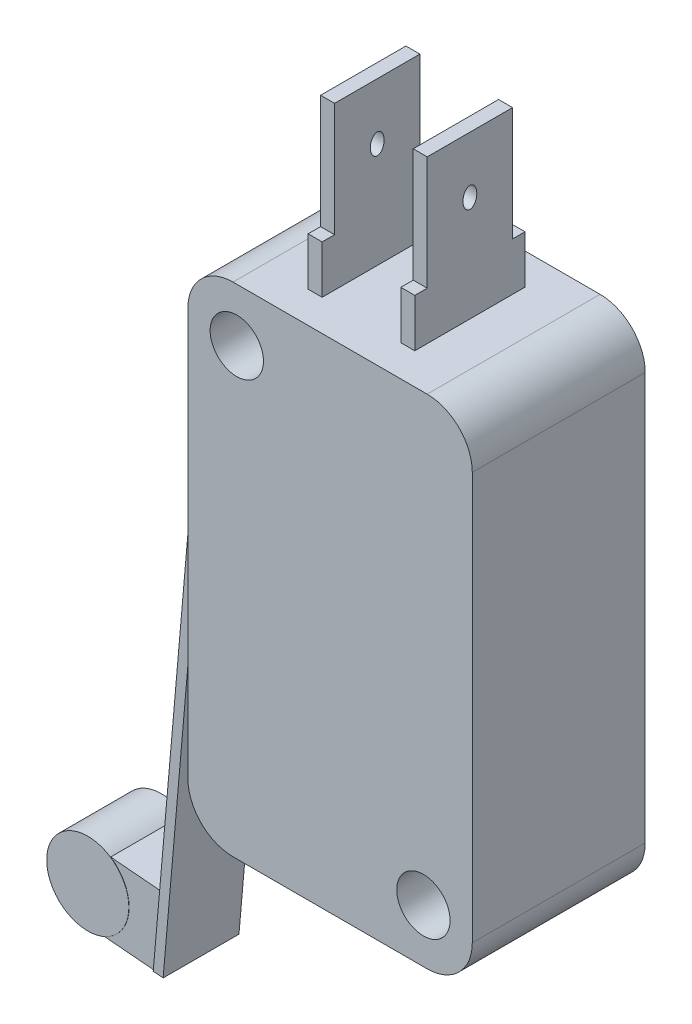
SolidWorks part; units mm, degrees
ref_plane "Front Plane" through (0, 0, 0) normal (0, 0, 1) x (1, 0, 0)
ref_plane "Top Plane" through (0, 0, 0) normal (0, 1, 0) x (1, 0, 0)
ref_plane "Right Plane" through (0, 0, 0) normal (1, 0, 0) x (0, 0, -1)
sketch "Sketch1" plane through (0, 0, 0) normal (0, 0, 1) x (1, 0, 0)
  line L1 (5.46, -14) -> (-5.46, -14)
  line L2 (8, -11.46) -> (8, 11.46)
  line L3 (5.46, 14) -> (-5.46, 14)
  line L4 (-8, -11.46) -> (-8, 11.46)
  line L5 (8, -14) -> (-8, 14) construction
  line L6 (8, 14) -> (-8, -14) construction
  arc A0 (5.46, -14) -> (8, -11.46) centre (5.46, -11.46) ccw
  arc A1 (-5.46, -14) -> (-8, -11.46) centre (-5.46, -11.46) cw
  arc A2 (8, 11.46) -> (5.46, 14) centre (5.46, 11.46) ccw
  arc A3 (-5.46, 14) -> (-8, 11.46) centre (-5.46, 11.46) ccw
  point P1 (0, 0)
  dimension "D3" = 2.54
  dimension "D1" = 28
  dimension "D2" = 16
extrude "Boss-Extrude1" add sketch "Sketch1" along normal mid plane 9.7282
ref_plane "Plane1" through (3, 0, 0) normal (1, 0, 0) x (0, 0, -1)
ref_plane "Plane2" through (-3, 0, 0) normal (1, 0, 0) x (0, 0, -1)
sketch "Sketch2" plane through (3, 0, 0) normal (1, 0, 0) x (0, 0, -1)
  line L0 (0, -3.2714) -> (0, 26.117) construction
  line L1 (-3.1, 14) -> (-3.1, 16.7)
  line L2 (-4.8641, 14) -> (4.8641, 14) construction
  line L3 (-3.1, 16.7) -> (-2.4, 16.7)
  line L4 (-2.4, 16.7) -> (-2.4, 23.1)
  line L5 (-2.4, 23.1) -> (2.4, 23.1)
  line L6 (2.4, 16.7) -> (2.4, 23.1)
  line L7 (3.1, 16.7) -> (2.4, 16.7)
  line L8 (3.1, 14) -> (3.1, 16.7)
  line L9 (3.1, 14) -> (-3.1, 14)
  ellipse E0 centre (0, 19.925) end of major axis (0, 19.3408) minor radius 0.388
  point P18 (0, 23.1)
  dimension "D1" = 6.2
  dimension "D2" = 0.5842
  dimension "D3" = 0.388
  dimension "D4" = 4.8
  dimension "D5" = 9.1
  dimension "D6" = 3.175
  dimension "D7" = 6.4
sketch "Sketch4" plane through (-3, 0, 0) normal (1, 0, 0) x (0, 0, -1)
  line L8 (2.4, 16.7) -> (2.4, 23.1)
  line L9 (3.1, 16.7) -> (2.4, 16.7)
  line L10 (3.1, 14) -> (3.1, 16.7)
  line L11 (-3.1, 14) -> (3.1, 14)
  line L12 (-3.1, 16.7) -> (-3.1, 14)
  line L13 (-2.4, 16.7) -> (-3.1, 16.7)
  line L14 (-2.4, 23.1) -> (-2.4, 16.7)
  line L15 (2.4, 23.1) -> (-2.4, 23.1)
  line L16 (2.4, 16.7) -> (2.4, 23.1)
  line L17 (3.1, 16.7) -> (2.4, 16.7)
  line L18 (3.1, 14) -> (3.1, 16.7)
  line L19 (-3.1, 14) -> (3.1, 14)
  line L20 (-3.1, 16.7) -> (-3.1, 14)
  line L21 (-2.4, 16.7) -> (-3.1, 16.7)
  line L22 (-2.4, 23.1) -> (-2.4, 16.7)
  line L23 (2.4, 23.1) -> (-2.4, 23.1)
  ellipse E1 centre (0, 19.925) end of major axis (0, 19.3408) minor radius 0.388
  ellipse E2 centre (0, 19.925) end of major axis (0, 19.3408) minor radius 0.388
  dimension "D1" = 0
  dimension "D2" = 0
extrude "Boss-Extrude2" add sketch "Sketch2" against normal blind 0.7874
extrude "Boss-Extrude3" add sketch "Sketch4" along normal blind 0.7874
sketch "Sketch5" plane through (0, 0, 0) normal (0, 0, 1) x (1, 0, 0)
  line L0 (-8, 2.7732) -> (-10.29, 2.7732)
  line L1 (-8, 11.46) -> (-8, -11.46) construction
  line L3 (-12.6809, -24.5544) -> (-12.1242, -24.6031)
  line L4 (-12.1242, -24.6031) -> (-9.778, 2.2144)
  line L5 (-9.778, 2.2144) -> (-8, 2.2144)
  line L6 (-8, 2.7732) -> (-8, 2.2144)
  line L7 (-10.29, 2.7732) -> (-12.6809, -24.5544)
  line L8 (5.46, 14) -> (-5.46, 14) construction
  line L9 (-12.6809, -24.5544) -> (-15.5055, -24.3073)
  line L11 (-9.1132, -22.8268) -> (-20.1032, -21.8653) construction
  line L12 (-15.6313, -25.7451) -> (-14.8767, -17.1199) construction
  line L13 (-15.1513, -20.2588) -> (-12.3267, -20.5059)
  circle A0 centre (-16.4258, -22.187) radius 2.3114
  point P19 (-15.1513, -20.2588)
  point P20 (-14.8145, -19.9309)
  point P21 (-15.5055, -24.3073)
  point P22 (0, 0)
  point P23 (0, 0)
  dimension "D7" = 4.6228
  dimension "D1" = 0.5588
  dimension "D2" = 0.5588
  dimension "D3" = 27.432
  dimension "D4" = 11.2268
  dimension "D5" = 1.778
  dimension "D6" = 95
  dimension "D8" = 4.064
  dimension "D9" = 3.937
extrude "Boss-Extrude5" add sketch "Sketch5" along normal mid plane 4.2672 contours L3 L4 L5 L6 L0 L7
extrude "Boss-Extrude6" add sketch "Sketch5<6>" along normal mid plane 4.1148 contours A0 L9 L7 L13 region at (-13.5159, -22.4416, 0)
sketch "Sketch5<6>" plane through (0, 0, 0) normal (0, 0, 1) x (1, 0, 0) same geometry as "Sketch5"
extrude "Boss-Extrude7" add sketch "Sketch5<7>" along normal mid plane 4.1402 contours A0 region at (-16.4258, -22.187, 0)
sketch "Sketch5<7>" plane through (0, 0, 0) normal (0, 0, 1) x (1, 0, 0) same geometry as "Sketch5"
sketch "Sketch6" plane through (0, 0, 4.8641) normal (0, 0, 1) x (1, 0, 0)
  line L0 (-14.5602, 0) -> (18.7301, 0) construction
  circle A0 centre (-5.25, 11) radius 1.5
  circle A1 centre (5.25, -11) radius 1.5
  dimension "D1" = 3
  dimension "D2" = 22
  dimension "D3" = 11
  dimension "D4" = 10.5
  dimension "D5" = 5.25
extrude "Cut-Extrude1" cut sketch "Sketch6" against normal through all
